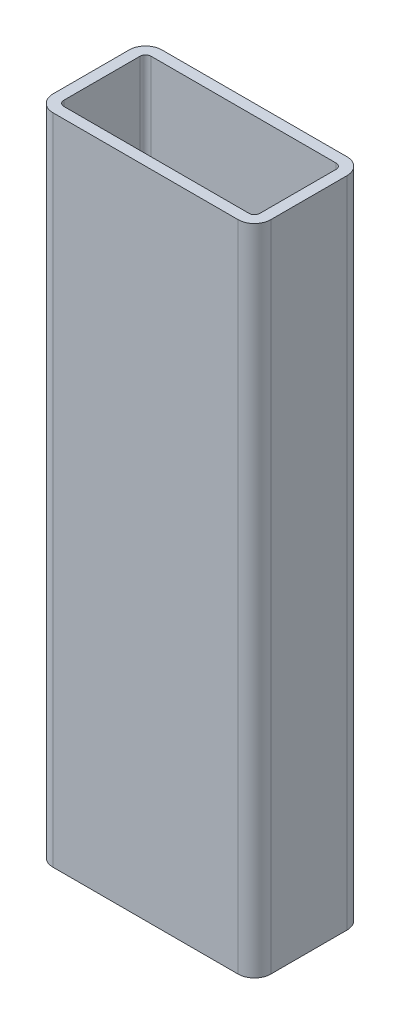
SolidWorks part; units mm, degrees
ref_plane "Спереди" through (0, 0, 0) normal (0, 0, 1) x (1, 0, 0)
ref_plane "Сверху" through (0, 0, 0) normal (0, 1, 0) x (1, 0, 0)
ref_plane "Справа" through (0, 0, 0) normal (1, 0, 0) x (0, 0, -1)
sketch "Эскиз1" plane through (0, 0, 0) normal (0, 1, 0) x (1, 0, 0)
  line L1 (3, 0) -> (37, 0)
  line L2 (0, 3) -> (0, 17)
  line L3 (3, 20) -> (37, 20)
  line L4 (40, 3) -> (40, 17)
  arc A0 (37, 0) -> (40, 3) centre (37, 3) ccw
  arc A1 (40, 17) -> (37, 20) centre (37, 17) ccw
  arc A2 (0, 17) -> (3, 20) centre (3, 17) cw
  arc A3 (0, 3) -> (3, 0) centre (3, 3) ccw
  point P13 (0, 0)
  dimension "D1" = 3
extrude "Вытянуть-Тонкостенный1" add sketch "Эскиз1" along normal blind 120 thin thin type one direction reverse wall 2
